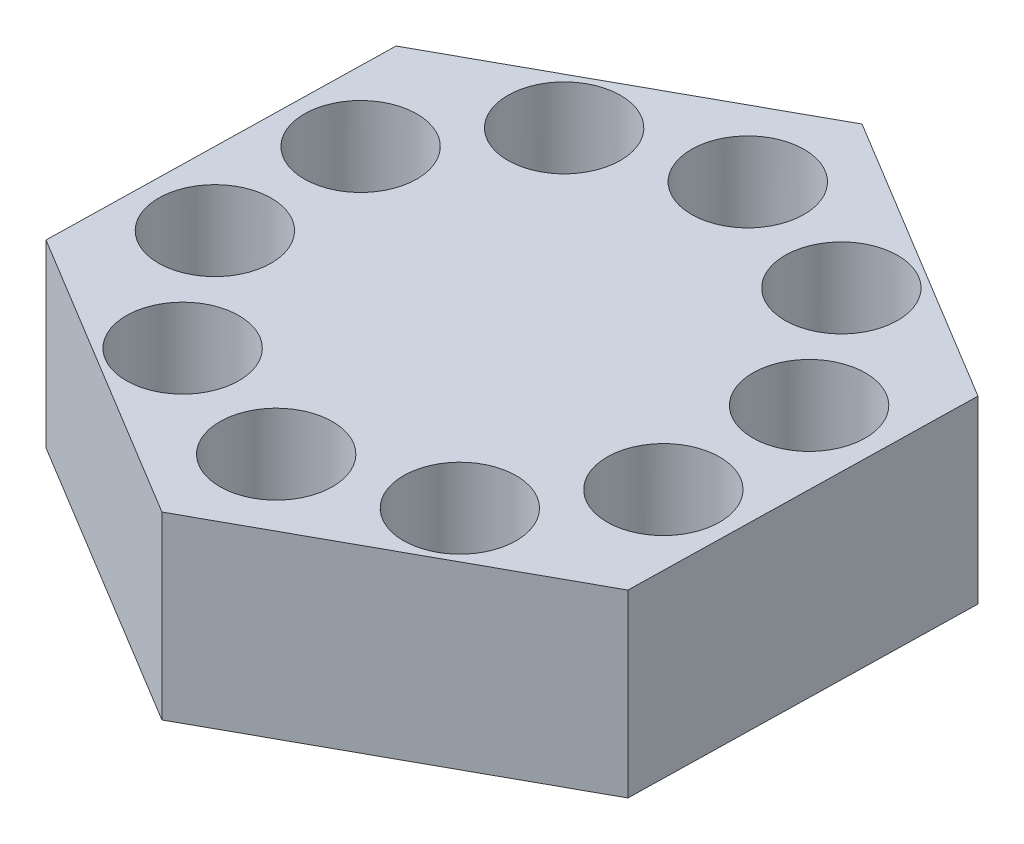
SolidWorks part; units mm, degrees
ref_plane "Front Plane" through (0, 0, 0) normal (0, 0, 1) x (1, 0, 0)
ref_plane "Top Plane" through (0, 0, 0) normal (0, 1, 0) x (1, 0, 0)
ref_plane "Right Plane" through (0, 0, 0) normal (1, 0, 0) x (0, 0, -1)
sketch "Sketch1" plane through (0, 0, 0) normal (0, 1, 0) x (1, 0, 0)
  line L1 (58.7925, -35.5751) -> (60.2052, 33.1283)
  line L2 (60.2052, 33.1283) -> (1.4127, 68.7033)
  line L3 (1.4127, 68.7033) -> (-58.7925, 35.5751)
  line L4 (-58.7925, 35.5751) -> (-60.2052, -33.1283)
  line L5 (-60.2052, -33.1283) -> (-1.4127, -68.7033)
  line L6 (-1.4127, -68.7033) -> (58.7925, -35.5751)
  circle A0 centre (0, 0) radius 59.5114 construction
extrude "Boss-Extrude1" add sketch "Sketch1" against normal blind 8.89 and the other way blind 27.178 contours L1 L2 L3 L4 L5 L6
sketch "Sketch3" plane through (0, 27.178, 0) normal (0, 1, 0) x (1, 0, 0)
  circle A0 centre (0, -47.226) radius 11.2895
extrude "Cut-Extrude1" cut sketch "Sketch3" against normal up to next
ref_axis "Axis2" through (0, 28.9814, 0) along (0, -1, 0)
pattern_circular "CirPattern1" count 10 over 360 about axis through (0, 28.9814, 0) along (0, -1, 0) of "Cut-Extrude1"
